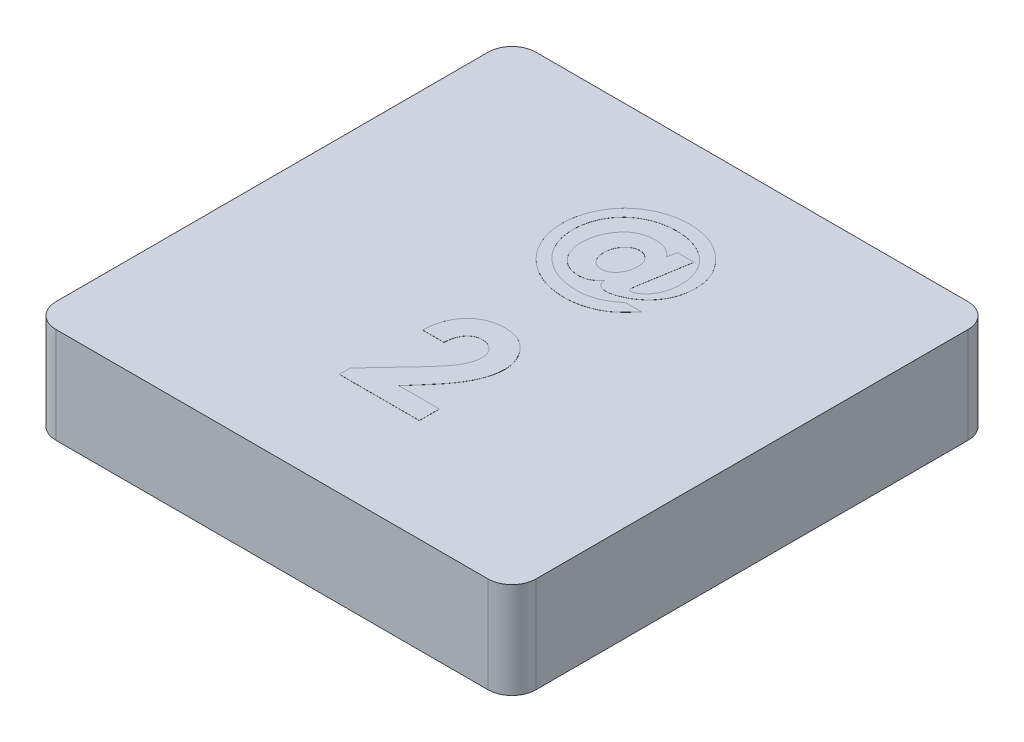
SolidWorks part; units mm, degrees
ref_plane "Front Plane" through (0, 0, 0) normal (0, 0, 1) x (1, 0, 0)
ref_plane "Top Plane" through (0, 0, 0) normal (0, 1, 0) x (1, 0, 0)
ref_plane "Right Plane" through (0, 0, 0) normal (1, 0, 0) x (0, 0, -1)
sketch "Sketch1" plane through (0, 0, 0) normal (0, 1, 0) x (1, 0, 0)
  line L0 (0, 0) -> (12.7, 0)
  line L1 (12.7, 0) -> (12.7, 12.7)
  line L2 (12.7, 12.7) -> (0, 12.7)
  line L3 (0, 12.7) -> (0, 0)
  dimension "D1" = 12.7
  dimension "D2" = 12.7
extrude "Boss-Extrude1" add sketch "Sketch1" along normal blind 2.54
fillet "Fillet1" radius 0.635 4 edges at (0, 1.27, -12.7) (12.7, 1.27, -12.7) (12.7, 1.27, 0) (0, 1.27, 0)
shell "Shell1" thickness 0.635 removed face at (6.35, 0, -6.35)
sketch "Sketch2" plane through (0, 1.905, 0) normal (0, -1, 0) x (-1, 0, 0)
  line L0 (-0.635, 6.35) -> (-12.065, 6.35) construction
  line L1 (-0.635, 12.065) -> (-0.635, 0.635) construction
  line L2 (-12.065, 0.635) -> (-12.065, 12.065) construction
  line L3 (-6.35, 0.635) -> (-6.35, 12.065) construction
  line L4 (-0.635, 0.635) -> (-12.065, 0.635) construction
  line L5 (-12.065, 12.065) -> (-0.635, 12.065) construction
  circle A0 centre (-6.35, 6.35) radius 2.54
  dimension "D1" = 5.08
extrude "Boss-Extrude2" add sketch "Sketch2" along normal up to surface (1.905 mm away) up to face at (6.35, 0, -6.35)
sketch "Sketch4" plane through (0, 2.54, 0) normal (0, 1, 0) x (1, 0, 0)
  line L0 (0, 12.065) -> (0, 0.635) construction
  line L1 (12.065, 12.7) -> (0.635, 12.7) construction
  line L2 (0.635, 0) -> (12.065, 0) construction
  text T0 "<b>2</b>"
  text T1 "<b>@</b>"
  dimension "D1" = 4.9022
  dimension "D2" = 5.334
  dimension "D3" = 5.207
  dimension "D4" = 2.7178
extrude "Boss-Extrude4" add sketch "Sketch4" along normal blind 0.0025
